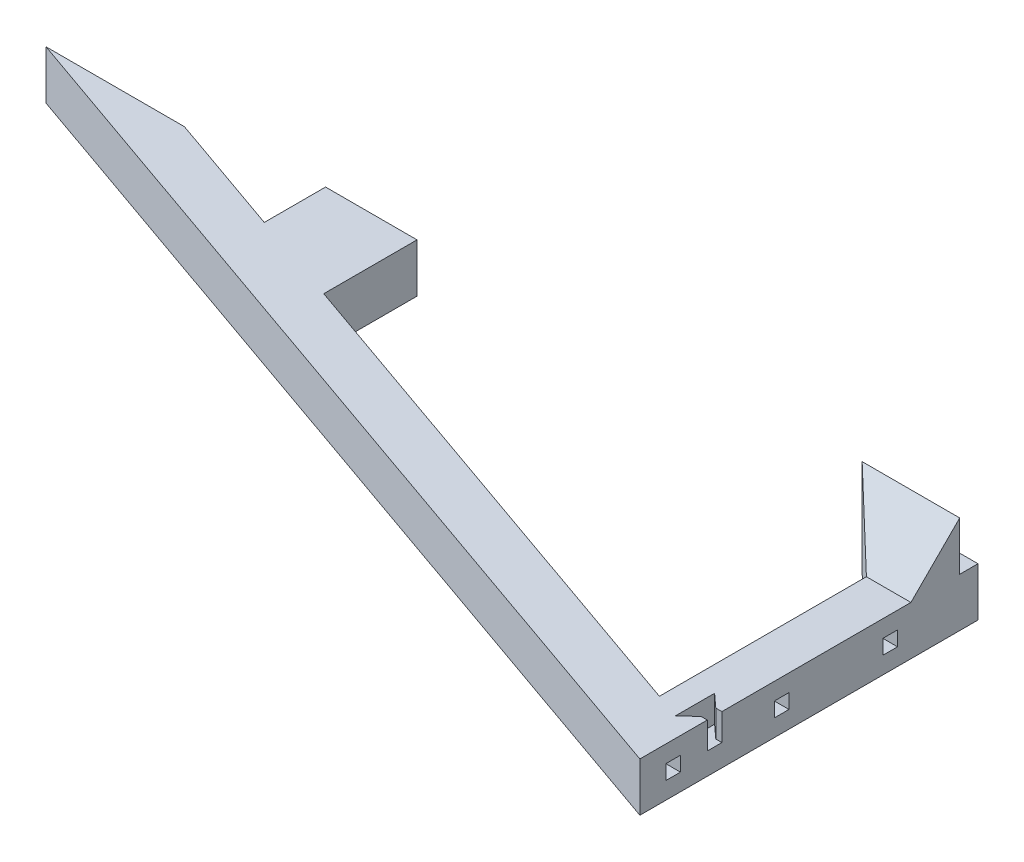
SolidWorks part; units mm, degrees
ref_plane "Přední rovina" through (0, 0, 0) normal (0, 0, 1) x (1, 0, 0)
ref_plane "Horní rovina" through (0, 0, 0) normal (0, 1, 0) x (1, 0, 0)
ref_plane "Pravá rovina" through (0, 0, 0) normal (1, 0, 0) x (0, 0, -1)
sketch "Skica2" plane through (0, 0, 0) normal (0, 1, 0) x (1, 0, 0)
  line L13 (0, 0) -> (0, -55.45)
  line L14 (0, -55.45) -> (-149.85, -3)
  line L15 (-149.85, -3) -> (-127.1478, -3)
  line L16 (-127.1478, -3) -> (-107, -10.0521)
  line L17 (-107, -10.0521) -> (-107, 0)
  line L18 (-107, 0) -> (-92, 0)
  line L19 (-92, 0) -> (-92, -15.3023)
  line L20 (-92, -15.3023) -> (-7.3, -44.9487)
  line L21 (-7.3, -44.9487) -> (-7.3, 0)
  line L22 (-7.3, 0) -> (0, 0)
  dimension "D1" = 55.45
  dimension "D2" = 149.85
  dimension "D3" = 7.5
  dimension "D4" = 15
  dimension "D5" = 7.3
  dimension "D6" = 3
  dimension "D7" = 7.5
  dimension "D8" = 84.7
extrude "Přidat vysunutím1" add sketch "Skica2" along normal blind 8
sketch "Skica3" plane through (0, 8, 0) normal (0, 1, 0) x (1, 0, 0)
  line L6 (0, -42) -> (-1, -42)
  line L7 (0, -55.45) -> (0, 0) construction
  line L8 (-1, -42) -> (-3.2, -40)
  line L9 (-3.2, -40) -> (-3.2, -46.4)
  line L10 (-3.2, -46.4) -> (-1, -44.4)
  line L11 (-1, -44.4) -> (0, -44.4)
  line L12 (0, -44.4) -> (0, -42)
  line L13 (0, 0) -> (-7.3, 0) construction
  dimension "D1" = 1
  dimension "D2" = 1
  dimension "D3" = 6.4
  dimension "D4" = 2.4
  dimension "D5" = 3.2
  dimension "D6" = 2
  dimension "40" = 40
extrude "Odebrat vysunutím1" cut sketch "Skica3" against normal blind 4.4
sketch "Skica5" plane through (0, 8, 0) normal (0, 1, 0) x (1, 0, 0)
  line L10 (0, -42) -> (0, 0) construction
  line L11 (0, -3) -> (-16, -3)
  line L12 (0, -3) -> (0, -11)
  line L13 (0, -11) -> (-16, -11)
  line L14 (-16, -3) -> (-16, -11)
  line L15 (0, 0) -> (-7.3, 0) construction
  dimension "D1" = 3
  dimension "D2" = 8
  dimension "D3" = 16
extrude "Přidat vysunutím2" add sketch "Skica5" against normal blind 16 from offset 8
sketch "Skica6" plane through (0, 0, 0) normal (1, 0, 0) x (0, 0, -1)
  line L3 (-11, 8) -> (-11, 16)
  line L4 (-11, 16) -> (-3, 16)
  line L5 (-3, 16) -> (-11, 8)
extrude "Odebrat vysunutím3" cut sketch "Skica6" against normal through all
sketch "Skica7" plane through (0, 0, 0) normal (0, -1, 0) x (1, 0, 0)
  line L3 (-16, 3) -> (-16, 11)
  line L4 (-16, 11) -> (-7.3, 11)
  line L5 (-7.3, 11) -> (-16, 3)
extrude "Odebrat vysunutím4" cut sketch "Skica7" against normal through all
sketch "Skica4" plane through (0, 0, 0) normal (1, 0, 0) x (0, 0, -1)
  line L0 (-3, 8) -> (0, 8) construction
  line L1 (-51.2, 5.2) -> (-48.8, 5.2)
  line L2 (-51.2, 5.2) -> (-51.2, 2.8)
  line L3 (-51.2, 2.8) -> (-48.8, 2.8)
  line L4 (-48.8, 5.2) -> (-48.8, 2.8)
  line L5 (-33.4, 5.2) -> (-31, 5.2)
  line L6 (-33.4, 5.2) -> (-33.4, 2.8)
  line L7 (-33.4, 2.8) -> (-31, 2.8)
  line L8 (-31, 5.2) -> (-31, 2.8)
  line L9 (-15.6, 5.2) -> (-13.2, 5.2)
  line L10 (-15.6, 5.2) -> (-15.6, 2.8)
  line L11 (-15.6, 2.8) -> (-13.2, 2.8)
  line L12 (-13.2, 5.2) -> (-13.2, 2.8)
  line L13 (-55.45, 8) -> (-44.4, 8) construction
  line L14 (0, 8) -> (0, 0) construction
  dimension "D1" = 2.4
  dimension "D2" = 2.4
  dimension "D3" = 2.4
  dimension "D4" = 2.4
  dimension "D5" = 2.4
  dimension "D6" = 2.4
  dimension "D7" = 2.8
  dimension "D8" = 2.8
  dimension "D9" = 2.8
  dimension "D10" = 13.2
  dimension "D11" = 15.4
  dimension "D12" = 15.4
extrude "Odebrat vysunutím2" cut sketch "Skica4" against normal blind 4.4
